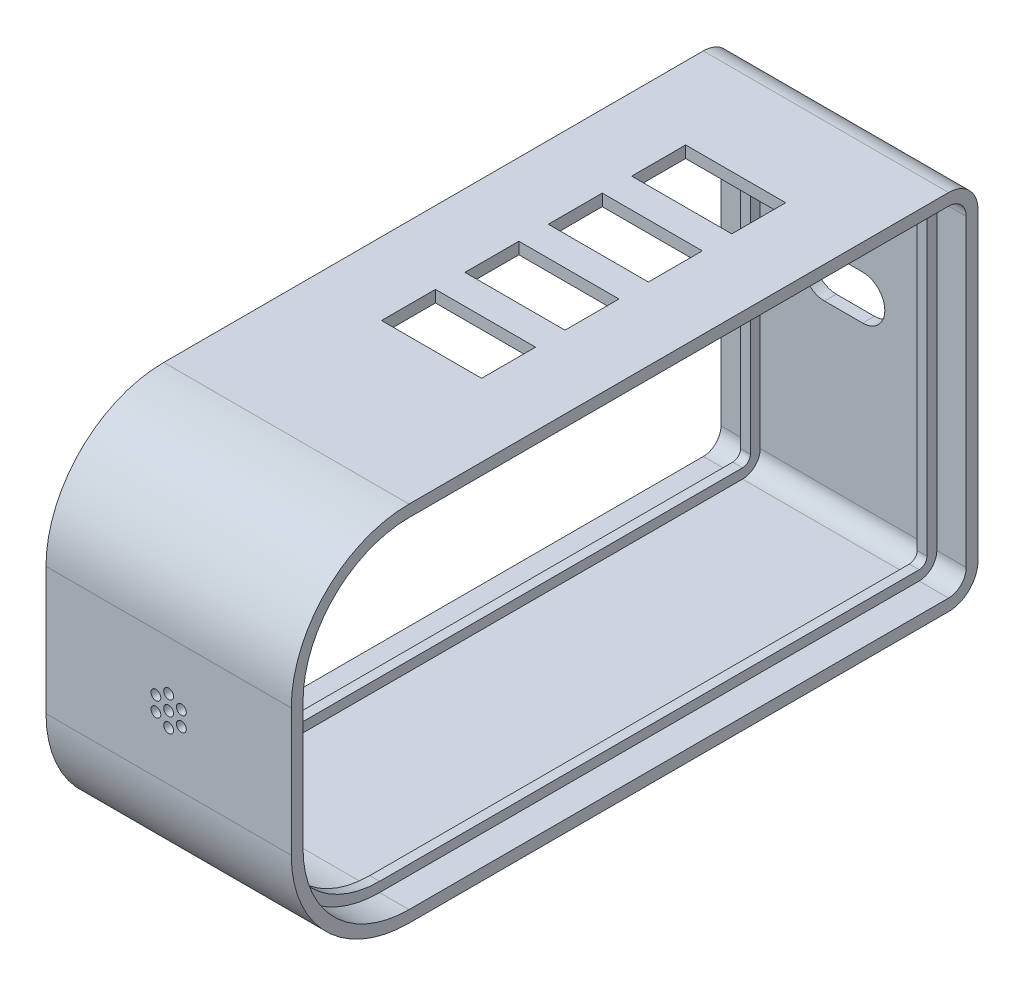
SolidWorks part; units mm, degrees
ref_plane "Front Plane" through (0, 0, 0) normal (0, 0, 1) x (1, 0, 0)
ref_plane "Top Plane" through (0, 0, 0) normal (0, 1, 0) x (1, 0, 0)
ref_plane "Right Plane" through (0, 0, 0) normal (1, 0, 0) x (0, 0, -1)
sketch "Sketch1" plane through (0, 0, 0) normal (1, 0, 0) x (0, 0, -1)
  line L1 (-23, -18.5) -> (32, -18.5)
  line L2 (-35, -6.5) -> (-35, 6.5)
  line L3 (-23, 18.5) -> (32, 18.5)
  line L4 (35, -15.5) -> (35, 15.5)
  line L5 (-35, -18.5) -> (35, 18.5) construction
  line L6 (-35, 18.5) -> (35, -18.5) construction
  arc A0 (32, -18.5) -> (35, -15.5) centre (32, -15.5) ccw
  arc A1 (32, 18.5) -> (35, 15.5) centre (32, 15.5) cw
  arc A2 (-23, -18.5) -> (-35, -6.5) centre (-23, -6.5) cw
  arc A3 (-35, 6.5) -> (-23, 18.5) centre (-23, 6.5) cw
  point P0 (0, 0)
  dimension "D3" = 3
  dimension "D4" = 12
  dimension "D1" = 70
  dimension "D2" = 37
extrude "Boss-Extrude1" add sketch "Sketch1" along normal mid plane 25
sketch "Sketch2" plane through (-12.5, 0, 0) normal (-1, 0, 0) x (0, 0, 1)
  line L8 (-33.8, 15.5) -> (-33.8, -15.5)
  line L9 (-32, -17.3) -> (23, -17.3)
  line L10 (33.8, -6.5) -> (33.8, 6.5)
  line L11 (23, 17.3) -> (-32, 17.3)
  line L12 (-33.8, 15.5) -> (-33.8, -15.5)
  line L13 (-32, -17.3) -> (23, -17.3)
  line L14 (33.8, -6.5) -> (33.8, 6.5)
  line L15 (23, 17.3) -> (-32, 17.3)
  arc A2 (-32, 17.3) -> (-33.8, 15.5) centre (-32, 15.5) ccw
  arc A3 (-32, 17.3) -> (-33.8, 15.5) centre (-32, 15.5) ccw
  arc A4 (-33.8, -15.5) -> (-32, -17.3) centre (-32, -15.5) ccw
  arc A5 (-33.8, -15.5) -> (-32, -17.3) centre (-32, -15.5) ccw
  arc A8 (23, -17.3) -> (33.8, -6.5) centre (23, -6.5) ccw
  arc A9 (23, -17.3) -> (33.8, -6.5) centre (23, -6.5) ccw
  arc A10 (33.8, 6.5) -> (23, 17.3) centre (23, 6.5) ccw
  arc A11 (33.8, 6.5) -> (23, 17.3) centre (23, 6.5) ccw
  dimension "D1" = 1.2
extrude "Cut-Extrude1" cut sketch "Sketch2" against normal up to surface (25 mm away) up to face at (12.5, 0, -1.784)
sketch "Sketch3" plane through (0, 18.5, 0) normal (0, 1, 0) x (1, 0, 0)
  line L0 (0, -35) -> (0, 35) construction
  line L1 (12.5, -35) -> (-12.5, -35) construction
  line L2 (12.5, 35) -> (-12.5, 35) construction
  line L3 (5.1, 17.3) -> (-5.1, 17.3)
  line L4 (5.1, 17.3) -> (5.1, 22.8)
  line L5 (-5.1, 17.3) -> (-5.1, 22.8)
  line L6 (5.1, 22.8) -> (-5.1, 22.8)
  line L7 (5.1, 17.3) -> (-5.1, 22.8) construction
  line L8 (-5.1, 17.3) -> (5.1, 22.8) construction
  line L9 (12.5, 33.8) -> (-12.5, 33.8) construction
  line L10 (5.1, 8.8) -> (-5.1, 8.8)
  line L11 (5.1, 8.8) -> (5.1, 14.3)
  line L12 (5.1, 14.3) -> (-5.1, 14.3)
  line L13 (-5.1, 8.8) -> (-5.1, 14.3)
  line L14 (0, -43.5) -> (0, 26.5) construction
  line L15 (5.1, 0.3) -> (-5.1, 0.3)
  line L16 (5.1, 0.3) -> (5.1, 5.8)
  line L17 (5.1, 5.8) -> (-5.1, 5.8)
  line L18 (-5.1, 0.3) -> (-5.1, 5.8)
  line L19 (0, -52) -> (0, 18) construction
  line L20 (5.1, -8.2) -> (-5.1, -8.2)
  line L21 (5.1, -8.2) -> (5.1, -2.7)
  line L22 (5.1, -2.7) -> (-5.1, -2.7)
  line L23 (-5.1, -8.2) -> (-5.1, -2.7)
  line L24 (0, -60.5) -> (0, 9.5) construction
  point P7 (0, 20.05)
  dimension "D1" = 5.5
  dimension "D2" = 11
  dimension "D3" = 10.2
  dimension "D5" = 3
  dimension "D4" = 4
extrude "Cut-Extrude2" cut sketch "Sketch3" against normal up to surface (1.2 mm away) up to face at (0, 17.3, -4.5)
sketch "Sketch4" plane through (0, 0, -35) normal (0, 0, -1) x (-1, 0, 0)
  line L0 (0, 18.5) -> (0, -18.5) construction
  line L1 (-12.5, 18.5) -> (12.5, 18.5) construction
  line L2 (-12.5, -18.5) -> (12.5, -18.5) construction
  line L3 (-4.2, 14.3) -> (4.2, 14.3)
  line L4 (-4.2, 14.3) -> (-4.2, 9.3)
  line L5 (4.2, 14.3) -> (4.2, 9.3)
  line L6 (-4.2, 9.3) -> (4.2, 9.3)
  line L7 (-4.2, 14.3) -> (4.2, 9.3) construction
  line L8 (4.2, 14.3) -> (-4.2, 9.3) construction
  line L9 (-1.95, 5.3) -> (1.95, 5.3)
  line L12 (-1.95, 0.8) -> (1.95, 0.8)
  line L13 (-1.95, 5.3) -> (1.95, 0.8) construction
  line L14 (1.95, 5.3) -> (-1.95, 0.8) construction
  line L15 (-12.5, 17.3) -> (12.5, 17.3) construction
  arc A0 (1.95, 5.3) -> (1.95, 0.8) centre (1.95, 3.05) cw
  arc A1 (-1.95, 5.3) -> (-1.95, 0.8) centre (-1.95, 3.05) ccw
  point P7 (0, 11.8)
  point P8 (0, 3.05)
  point P20 (-4.2, 3.05)
  point P21 (4.2, 3.05)
  point P22 (0, 0)
  dimension "D1" = 5
  dimension "D2" = 3
  dimension "D3" = 8.4
  dimension "D4" = 8.4
  dimension "D5" = 4.5
  dimension "D6" = 12
extrude "Cut-Extrude3" cut sketch "Sketch4" against normal up to surface (1.2 mm away) up to face at (0, 0, -33.8)
sketch "Sketch5" plane through (0, 0, 35) normal (0, 0, 1) x (1, 0, 0)
  circle A0 centre (0, 0) radius 0.5
  point P5 (0, 0)
  dimension "D2" = 1
extrude "Cut-Extrude4" cut sketch "Sketch5" against normal up to surface (1.2 mm away) up to face at (0, 0, 33.8)
sketch "Sketch6" plane through (0, 0, 35) normal (0, 0, 1) x (1, 0, 0)
  circle A0 centre (0, 1.5) radius 0.5
  circle A1 centre (0, 0) radius 0.5 construction
  circle A2 centre (1.299, 0.75) radius 0.5
  circle A3 centre (1.299, -0.75) radius 0.5
  circle A4 centre (0, -1.5) radius 0.5
  circle A5 centre (-1.299, -0.75) radius 0.5
  circle A6 centre (-1.299, 0.75) radius 0.5
  point P5 (0, 0)
  point P18 (0, 0)
  dimension "D1" = 1.5
  dimension "D2" = 6
extrude "Cut-Extrude6" cut sketch "Sketch6" against normal up to surface (1.2 mm away) up to face at (0.5, 0, 33.8)
sketch "Sketch7" plane through (0, 0, 33.8) normal (0, 0, -1) x (-1, 0, 0)
  line L0 (0, 2.9453) -> (0, -3.3771) construction
  line L1 (0.0987, 0.5) -> (5.4522, 0.5) construction
  circle A0 centre (0, 0) radius 0.5 construction
  circle A1 centre (-5.75, -0.75) radius 1.25 construction
  circle A2 centre (5.75, -0.75) radius 1.25 construction
  circle A3 centre (-5.75, -0.75) radius 1.75
  circle A4 centre (5.75, -0.75) radius 1.75
  point P2 (0, 0.5)
  point P8 (-7, -0.75)
  dimension "D1" = 2.5
  dimension "D2" = 7
  dimension "D3" = 0.5
  dimension "D4" = 0.5
extrude "Boss-Extrude2" add sketch "Sketch7" along normal blind 2.5
sketch "Sketch8" plane through (0, 0, 31.3) normal (0, 0, -1) x (-1, 0, 0)
  circle A2 centre (-5.75, -0.75) radius 0.75
  circle A3 centre (-5.75, -0.75) radius 0.75
  circle A5 centre (5.75, -0.75) radius 0.75
  circle A6 centre (5.75, -0.75) radius 0.75
  dimension "D1" = 1
  dimension "D2" = 1
extrude "Cut-Extrude7" cut sketch "Sketch8" against normal blind 3
ref_plane "Plane5" through (9.5, 0, 0) normal (1, 0, 0) x (0, 0, -1)
sketch "Sketch9" plane through (9.5, 0, 0) normal (1, 0, 0) x (0, 0, -1)
  line L0 (-33.8, -6.5) -> (-33.8, 6.5) construction
  line L1 (-23, 17.3) -> (32, 17.3) construction
  line L2 (33.8, 15.5) -> (33.8, -15.5) construction
  line L3 (32, -17.3) -> (-23, -17.3) construction
  line L4 (-33.8, -6.5) -> (-33.8, 6.5)
  line L5 (-23, 17.3) -> (32, 17.3)
  line L6 (33.8, 15.5) -> (33.8, -15.5)
  line L7 (32, -17.3) -> (-23, -17.3)
  line L8 (-32.8, -6.5) -> (-32.8, 6.5)
  line L9 (-23, 16.3) -> (32, 16.3)
  line L10 (32.8, 15.5) -> (32.8, -15.5)
  line L11 (32, -16.3) -> (-23, -16.3)
  arc A0 (-23, 17.3) -> (-33.8, 6.5) centre (-23, 6.5) ccw construction
  arc A1 (33.8, 15.5) -> (32, 17.3) centre (32, 15.5) ccw construction
  arc A2 (32, -17.3) -> (33.8, -15.5) centre (32, -15.5) ccw construction
  arc A3 (-33.8, -6.5) -> (-23, -17.3) centre (-23, -6.5) ccw construction
  arc A4 (-23, 17.3) -> (-33.8, 6.5) centre (-23, 6.5) ccw
  arc A5 (33.8, 15.5) -> (32, 17.3) centre (32, 15.5) ccw
  arc A6 (32, -17.3) -> (33.8, -15.5) centre (32, -15.5) ccw
  arc A7 (-33.8, -6.5) -> (-23, -17.3) centre (-23, -6.5) ccw
  arc A8 (-23, 16.3) -> (-32.8, 6.5) centre (-23, 6.5) ccw
  arc A9 (32.8, 15.5) -> (32, 16.3) centre (32, 15.5) ccw
  arc A10 (32, -16.3) -> (32.8, -15.5) centre (32, -15.5) ccw
  arc A11 (-32.8, -6.5) -> (-23, -16.3) centre (-23, -6.5) ccw
  dimension "D1" = 1
extrude "Boss-Extrude3" add sketch "Sketch9" against normal blind 1
mirror "Mirror1" about plane through (0, 0, 0) normal (1, 0, 0) of "Boss-Extrude3"
